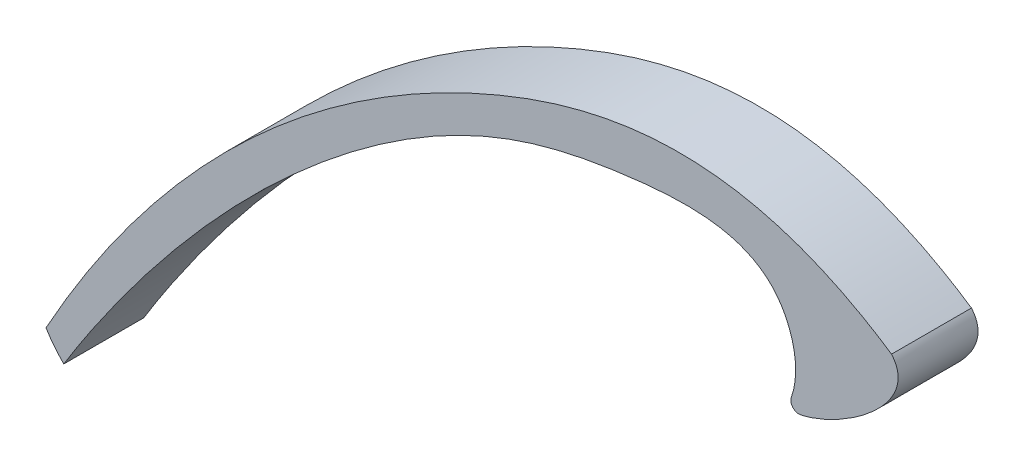
SolidWorks part; units mm, degrees
ref_plane "Front Plane" through (0, 0, 0) normal (0, 0, 1) x (1, 0, 0)
ref_plane "Top Plane" through (0, 0, 0) normal (0, 1, 0) x (1, 0, 0)
ref_plane "Right Plane" through (0, 0, 0) normal (1, 0, 0) x (0, 0, -1)
sketch "Sketch1" plane through (0, 0, 0) normal (0, 0, 1) x (1, 0, 0)
  line L0 (32.5301, 38.4695) -> (159.6711, 38.4695) construction
  line L1 (209.3033, 411.3339) -> (475.6045, 425.2901) construction
  spline S0 degree 3 poles (-184.4831, 287.2795) (-203.4278, 291.4832) (-215.0206, 306.7912) (-214.9315, 326.1907) (-195.9858, 329.1363) (-179.461, 325.8695) (-164.0555, 315.2918) (-162.2274, 292.6861) (-184.4831, 287.2795) (-203.4278, 291.4832) (-215.0206, 306.7912) knots -0.42162 -0.301914 -0.195701 0 0.085887 0.20658 0.330229 0.422867 0.57838 0.698086 0.804299 1 1.085887 1.20658 1.330229 only from (-206.0676, 296.3749) to (-206.0676, 296.3749)
  spline S1 degree 3 poles (-240.4751, 285.7975) (-254.1703, 280.5499) (-238.2276, 301.7402) (-228.1258, 309.0106) (-219.1047, 303.5329) (-222.1652, 293.2711) (-233.2647, 289.7001) (-240.4751, 285.7975) (-254.1703, 280.5499) (-238.2276, 301.7402) knots -0.352974 -0.236621 -0.024314 0 0.311875 0.430644 0.526172 0.647026 0.763379 0.975686 1 1.311875 1.430644 1.526172 only from (-246.8848, 283.3998) to (-246.8848, 283.3998)
  spline S2 degree 2 poles (-172.9135, 338.4014) (-172.2632, 338.236) (-171.9146, 338.134) knots 0.963854 0.963854 0.963854 1 1 1
  spline S3 degree 3 poles (-159.6925, 282.2864) (-161.0929, 280.9397) (-162.4778, 280.1206) (-165.7161, 278.5382) (-165.695, 279.9397) (-187.7466, 271.4052) (-198.6402, 265.2716) (-200.2293, 268.6554) knots 0.241509 0.241509 0.241509 0.241509 0.306691 0.363397 0.759109 0.825044 1 1 1 1
  spline S4 degree 3 poles (-292.2378, 230.0771) (-280.8733, 248.3251) (-252.3342, 283.4659) (-206.9267, 291.9755) (-186.2265, 278.4214) knots 0 0 0 0 0.510785 1 1 1 1
  spline S5 degree 2 poles (-295.2976, 239.6353) (-294.7032, 230.0706) (-287.6253, 225.8865) knots 0 0 0 1 1 1
  spline S6 degree 3 poles (-292.817, 230.9596) (-279.3713, 255.2187) (-248.4059, 286.0704) (-205.4701, 293.3538) (-187.02, 280.9979) knots 0 0 0 0 0.593505 0.977243 0.977243 0.977243 0.977243
  spline S7 degree 3 poles (-187.02, 280.9979) (-186.5597, 280.4625) (-184.2293, 275.1765) (-196.5679, 267.9496) (-200.2293, 268.6554) knots 0.123396 0.123396 0.123396 0.123396 0.21858 1 1 1 1
  spline S8 degree 3 poles (-287.6253, 225.8865) (-270.1892, 244.3026) (-250.4055, 277.8785) (-205.4589, 282.7503) (-200.2293, 268.6554) knots 0 0 0 0 0.680162 1 1 1 1
  spline S9 degree 3 poles (-178.7954, 335.4472) (-178.2405, 336.4742) (-178.085, 337.7265) (-178.3289, 339.2044) knots 0.635258 0.635258 0.635258 0.635258 1 1 1 1
  spline S10 degree 3 poles (-171.9146, 338.134) (-164.5117, 335.5557) (-152.7324, 324.6737) (-150.4342, 302.0933) (-156.601, 285.9993) (-159.6925, 282.2864) knots 0.005203 0.005203 0.005203 0.005203 0.309691 0.684335 0.866632 0.866632 0.866632 0.866632
  spline S11 degree 2 poles (-178.3822, 336.5151) (-180.1607, 332.8673) (-176.5907, 330.3959) knots 0 0 0 1 1 1
  spline S12 degree 3 poles (-172.9135, 338.4014) (-180.0858, 339.9411) (-200.5264, 338.5739) (-245.0517, 301.809) (-276.403, 269.1613) (-295.2976, 239.6353) knots 0.003532 0.003532 0.003532 0.003532 0.126811 0.380842 1 1 1 1
  spline S13 degree 3 poles (-176.5907, 330.3959) (-170.2528, 327.7787) (-153.3823, 308.4889) (-162.0923, 277.0326) (-186.4473, 280.0925) knots 0.102568 0.102568 0.102568 0.102568 0.3499 1 1 1 1
  spline S14 degree 3 poles (-289.7078, 227.3494) (-277.7639, 241.982) (-260.0502, 264.5651) (-224.9109, 285.0911) (-201.3053, 280.5308) (-195.8261, 269.5609) knots 0 0 0 0 0.479712 0.718046 1 1 1 1
  dimension "D1" = 31.2442
extrude "Boss-Extrude2" add sketch "Sketch1" along normal mid plane 10 contours S7 S6 S5 S4 | S5 S14 S7 S4 | S14 S5 S8 S7 region at (-249.5542, 267.9053, 0) region at (-247.9592, 277.218, 0) region at (-249.2039, 271.3107, 0)
sketch "Sketch2" plane through (0, 0, 5) normal (0, 0, 1) x (1, 0, 0)
  parabola Q0 (-292.817, 230.9596) -> (-287.6253, 225.8865) focus (-286.1123, 233.7666) apex (-291.5839, 229.2259) construction
  spline S0 degree 3 poles (-290.591, 228.1473) (-282.1629, 241.8476) (-263.9672, 264.6742) (-236.8177, 280.7449) (-219.2398, 284.3803) (-200.4815, 285.0933) (-197.9971, 272.3404) (-200.2293, 268.6554) knots 0 0 0 0 0.444555 0.62757 0.754797 0.896888 1 1 1 1
  spline S1 degree 3 poles (-200.2293, 268.6554) (-170.5104, 254.0729) (-317.6656, 183.5565) (-290.591, 228.1473) knots 0 0 0 0 1 1 1 1
extrude "Cut-Extrude1" cut sketch "Sketch2" against normal blind 10 and the other way blind 10
fillet "Fillet1" radius 1 1 edges
